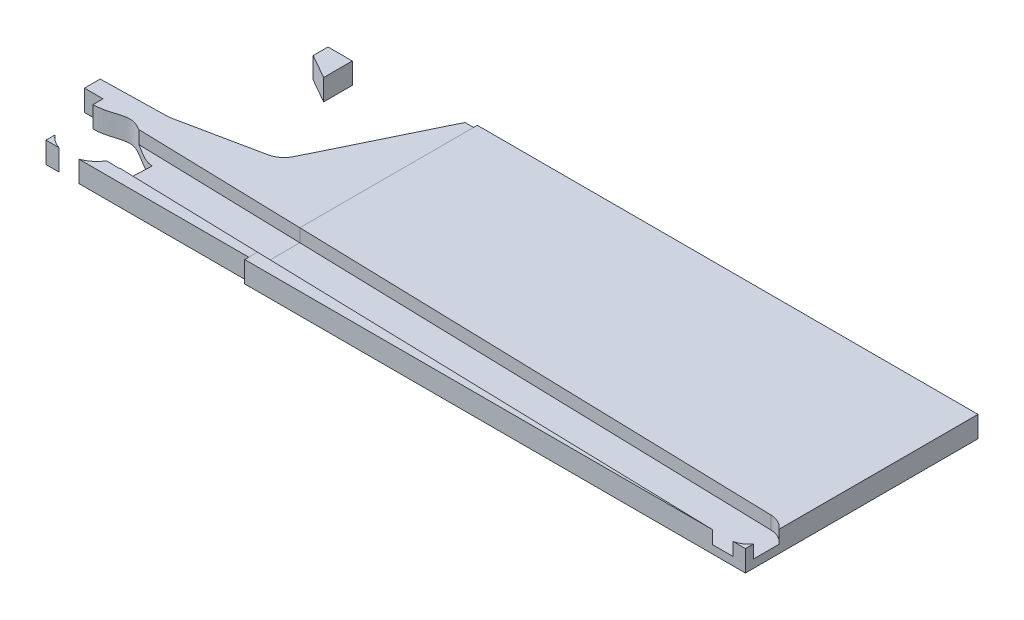
SolidWorks part; units mm, degrees
material "Yellow Foam"
ref_plane "Front Plane" through (0, 0, 0) normal (0, 0, 1) x (1, 0, 0)
ref_plane "Top Plane" through (0, 0, 0) normal (0, 1, 0) x (1, 0, 0)
ref_plane "Right Plane" through (0, 0, 0) normal (1, 0, 0) x (0, 0, -1)
ref_axis "Axis1" through (0, -55, 0) along (0, 1, 0)
sketch "Sketch1" plane through (0, 0, 0) normal (0, 1, 0) x (1, 0, 0)
  line L31 (-871.8204, -76.6493) -> (-871.6411, -114.2903)
  line L32 (-871.6411, -114.2903) -> (-827.3051, -114.2903)
  line L33 (-827.3051, -114.2903) -> (-827.3051, -138.4232)
  line L34 (-659.8294, -163.7482) -> (-662.9852, -239.4776)
  line L35 (-662.9852, -239.4776) -> (-809.7494, -236.0478)
  line L36 (-809.7494, -236.0478) -> (-809.7494, -268.615)
  line L37 (-809.7494, -268.615) -> (-323.0223, -268.615)
  line L38 (-323.0223, -268.615) -> (-323.0223, 270.9173)
  line L39 (-323.0223, 270.9173) -> (-343.5286, 270.9173)
  line L40 (-343.5286, 270.9173) -> (-477.9306, -5.236)
  line L41 (-513.3394, -32.7565) -> (-708.8347, -73.1063)
  line L225 (-708.8347, -73.1063) -> (-871.8204, -76.6493)
  line L235 (-606.7662, 194.8777) -> (-606.7662, 263.5188)
  line L236 (-606.7662, 263.5188) -> (-665.0489, 263.5188)
  line L237 (-665.0489, 263.5188) -> (-665.0489, 227.911)
  line L238 (-665.0489, 227.911) -> (-606.7662, 194.8777)
  arc A6 (-513.3394, -32.7565) -> (-477.9306, -5.236) centre (-523.608, 16.9949) ccw
  spline S2 degree 3 poles (-827.3051, -138.4232) (-792.2731, -138.4232) (-743.7974, -100.2282) (-689.2937, -162.5204) (-659.8294, -163.7482) knots 0 0 0 0 0.467855 1 1 1 1
  dimension "D1" = 50.8
  dimension "D2" = 323.0223
  dimension "D3" = 20.5063
  dimension "D4" = 134.402
  dimension "D5" = 35.4088
  dimension "D6" = 10.2686
  dimension "D7" = 83.1581
  dimension "D8" = 53.0632
  dimension "D9" = 3.1558
  dimension "D10" = 2.0637
  dimension "D11" = 100.9147
  dimension "D12" = 177.8828
  dimension "D13" = 17.5557
  dimension "D14" = 44.336
  dimension "D15" = 33.0333
  dimension "D16" = 35.6079
  dimension "D17" = 268.615
  dimension "D18" = 37.641
  dimension "D19" = 24.1329
  dimension "D20" = 25.325
  dimension "D21" = 72.2996
  dimension "D22" = 3.4298
extrude "Boss-Extrude1" add sketch "Sketch1" along normal blind 50.8
sketch "Sketch2" plane through (0, 0, 0) normal (0, 1, 0) x (1, 0, 0)
  line L3 (878.7536, -278.32) -> (-323.0223, -278.32)
  line L4 (878.7536, -278.32) -> (878.7536, 279.8794)
  line L5 (878.7536, 279.8794) -> (-323.0223, 279.8794)
  line L7 (-323.0223, -278.32) -> (-323.0223, 279.8794)
  dimension "D1" = 878.7536
  dimension "D2" = 323.0223
  dimension "D3" = 279.8794
  dimension "D4" = 278.32
extrude "Boss-Extrude2" add sketch "Sketch2" along normal blind 50.8 separate body
sketch "Sketch3" plane through (0, 0, 0) normal (1, 0, 0) x (0, 0, -1)
  line L0 (-134.976, 52.07) -> (-118.0051, 52.07) construction
  line L1 (-144.4291, 16.0006) -> (-137.4635, 50.0394) construction
  line L2 (-229.1881, 13.97) -> (-146.9165, 13.97) construction
  line L3 (-237.0036, 49.9241) -> (-231.6964, 16.1159) construction
  line L4 (-256.3833, 52.07) -> (-239.5119, 52.07) construction
  line L5 (-134.976, 52.07) -> (-118.0051, 52.07)
  line L6 (-144.4291, 16.0006) -> (-137.4635, 50.0394)
  line L7 (-229.1881, 13.97) -> (-146.9165, 13.97)
  line L8 (-237.0036, 49.9241) -> (-231.6964, 16.1159)
  line L9 (-256.3833, 52.07) -> (-239.5119, 52.07)
  line L10 (-256.3833, 52.07) -> (-256.3833, 56.6425)
  line L11 (-256.3833, 56.6425) -> (-118.0051, 56.6425)
  line L12 (-118.0051, 56.6425) -> (-118.0051, 52.07)
  ellipse E0 centre (-134.976, 49.53) end of major axis (-134.976, 46.99) minor radius 2.539 (-134.976, 52.07) -> (-137.4635, 50.0394) ccw construction
  ellipse E1 centre (-146.9165, 16.51) end of major axis (-146.9165, 19.05) minor radius 2.539 (-146.9165, 13.97) -> (-144.4291, 16.0006) ccw construction
  ellipse E2 centre (-229.1881, 16.51) end of major axis (-229.1881, 19.05) minor radius 2.539 (-231.6964, 16.1159) -> (-229.1881, 13.97) ccw construction
  ellipse E3 centre (-239.5119, 49.53) end of major axis (-239.5119, 46.99) minor radius 2.539 (-237.0036, 49.9241) -> (-239.5119, 52.07) ccw construction
  ellipse E4 centre (-134.976, 49.53) end of major axis (-134.976, 46.99) minor radius 2.539 (-134.976, 52.07) -> (-137.4635, 50.0394) ccw
  ellipse E5 centre (-146.9165, 16.51) end of major axis (-146.9165, 19.05) minor radius 2.539 (-146.9165, 13.97) -> (-144.4291, 16.0006) ccw
  ellipse E6 centre (-229.1881, 16.51) end of major axis (-229.1881, 19.05) minor radius 2.539 (-231.6964, 16.1159) -> (-229.1881, 13.97) ccw
  ellipse E7 centre (-239.5119, 49.53) end of major axis (-239.5119, 46.99) minor radius 2.539 (-237.0036, 49.9241) -> (-239.5119, 52.07) ccw
  dimension "D1" = 138.3782
  dimension "D2" = 4.5725
sketch "Sketch4" plane through (0, 0, 0) normal (0, 1, 0) x (1, 0, 0)
  line L0 (839.5874, -177.8548) -> (-739.1621, -134.6913) construction
  line L2 (-739.9143, -236.2085) -> (836.8117, -279.3451) construction
  line L3 (839.5874, -177.8548) -> (-780.0729, -133.5728)
  line L5 (-693.2285, -237.4857) -> (836.8117, -279.3451)
  arc A0 (836.8117, -279.3451) -> (839.5874, -177.8548) centre (838.2, -228.6) ccw construction
  arc A1 (836.8117, -279.3451) -> (839.5874, -177.8548) centre (838.2, -228.6) ccw
  arc A2 (-728.5697, -134.1152) -> (-693.2793, -237.5715) centre (-755.0274, -200.8875) ccw construction
  arc A3 (-780.0729, -133.5728) -> (-693.2285, -237.4857) centre (-755.0274, -200.8875) ccw
extrude "Cut-Extrude1" cut sketch "Sketch4" against normal blind 31.242 from surface starting at face at (-650.7571, 50.8, 84.3484)
sketch "Sketch5" plane through (0, 19.558, 0) normal (0, 1, 0) x (1, 0, 0)
  line L3 (-809.7494, -236.0478) -> (-809.7494, -247.4067)
  line L4 (-778.9339, -268.615) -> (-731.1208, -268.615)
  line L5 (-693.9967, -238.7529) -> (-809.7494, -236.0478)
  line L6 (-809.7494, -236.0478) -> (-809.7494, -247.4067)
  line L7 (-778.9339, -268.615) -> (-731.1208, -268.615)
  line L8 (-693.9967, -238.7529) -> (-809.7494, -236.0478)
  arc A2 (-809.7494, -247.4067) -> (-778.9339, -268.615) centre (-755.0274, -200.8875) ccw
  arc A3 (-731.1208, -268.615) -> (-693.9967, -238.7529) centre (-755.0274, -200.8875) ccw
  arc A4 (-809.7494, -247.4067) -> (-778.9339, -268.615) centre (-755.0274, -200.8875) ccw
  arc A5 (-731.1208, -268.615) -> (-693.9967, -238.7529) centre (-755.0274, -200.8875) ccw
  dimension "D1" = 0
extrude "Cut-Extrude2" cut sketch "Sketch5" against normal blind 34.544
